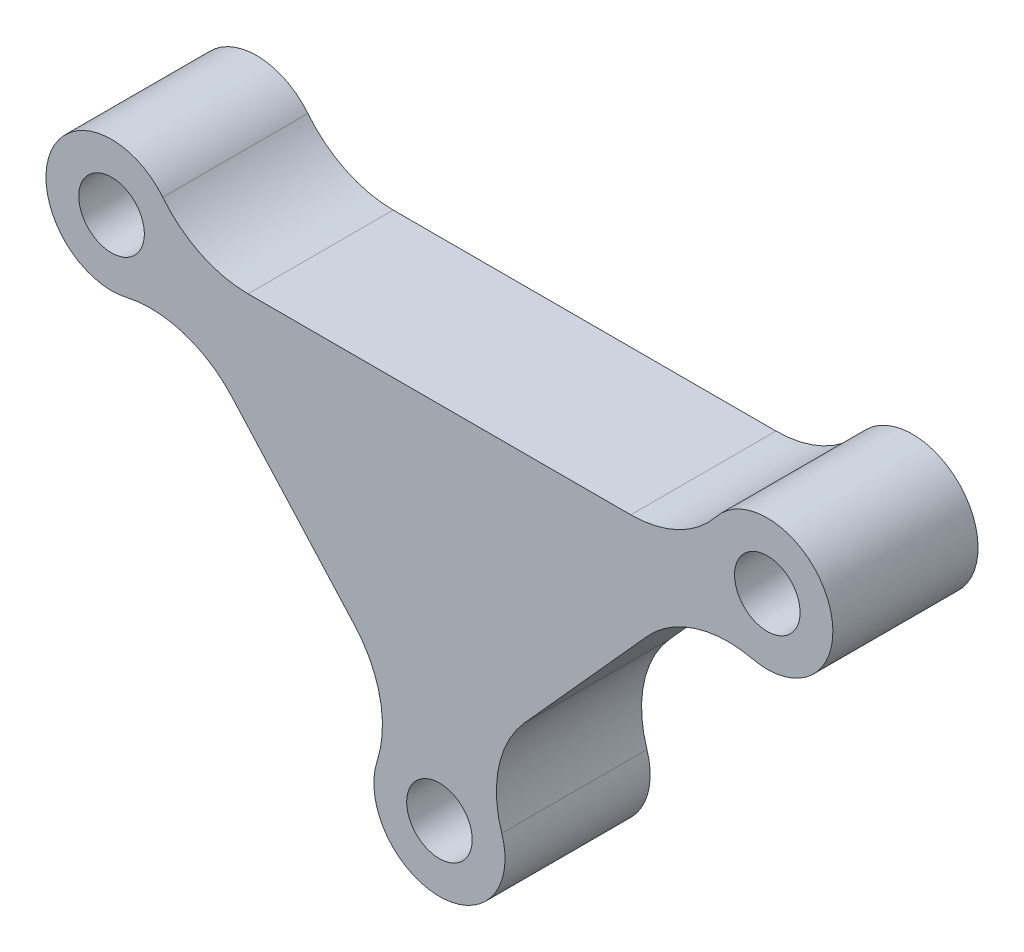
SolidWorks part; units mm, degrees
ref_plane "Plan de face" through (0, 0, 0) normal (0, 0, 1) x (1, 0, 0)
ref_plane "Plan de dessus" through (0, 0, 0) normal (0, 1, 0) x (1, 0, 0)
ref_plane "Plan de droite" through (0, 0, 0) normal (1, 0, 0) x (0, 0, -1)
sketch "Esquisse2" plane through (0, 0, 0) normal (0, 0, 1) x (1, 0, 0)
  line L0 (-13.5, 10) -> (13.5, 10)
  line L1 (13.5, 10) -> (0, -5)
  line L2 (0, -5) -> (-13.5, 10)
  line L3 (0, 0) -> (-13.5, 10) construction
  line L4 (0, 0) -> (13.5, 10) construction
  circle A0 centre (-15, 10) radius 3
  circle A1 centre (-15, 10) radius 1.5
  circle A2 centre (15, 10) radius 3
  circle A3 centre (15, 10) radius 1.5
  circle A4 centre (0, -6.5) radius 3
  circle A5 centre (0, -6.5) radius 1.5
  point P13 (0, 0)
  dimension "D2" = 3
  dimension "D3" = 6
  dimension "D1" = 5
  dimension "D4" = 10
  dimension "D5" = 15
extrude "Boss.-Extru.1" add sketch "Esquisse2" along normal blind 6.64 contours A4 L1 A2 L0 A0 L2 | L1 A5 L2 A4 | L1 A4 L2 | A3 | A1 | L0 L1 L2 | A2 | A0 | A4 | A5 region at (-15, 10, 0) region at (0, 5.0337, 0) region at (15, 10, 0) region at (0, -4.0518, 0) region at (-0.6346, -4.4193, 0)
fillet "Congé1" radius 5 6 edges at (-12, 10, 3.32) (-12.3081, 8.6757, 3.32) (-1.1454, -3.7273, 3.32) (12.3081, 8.6757, 3.32) (12, 10, 3.32) (1.1454, -3.7273, 3.32)
